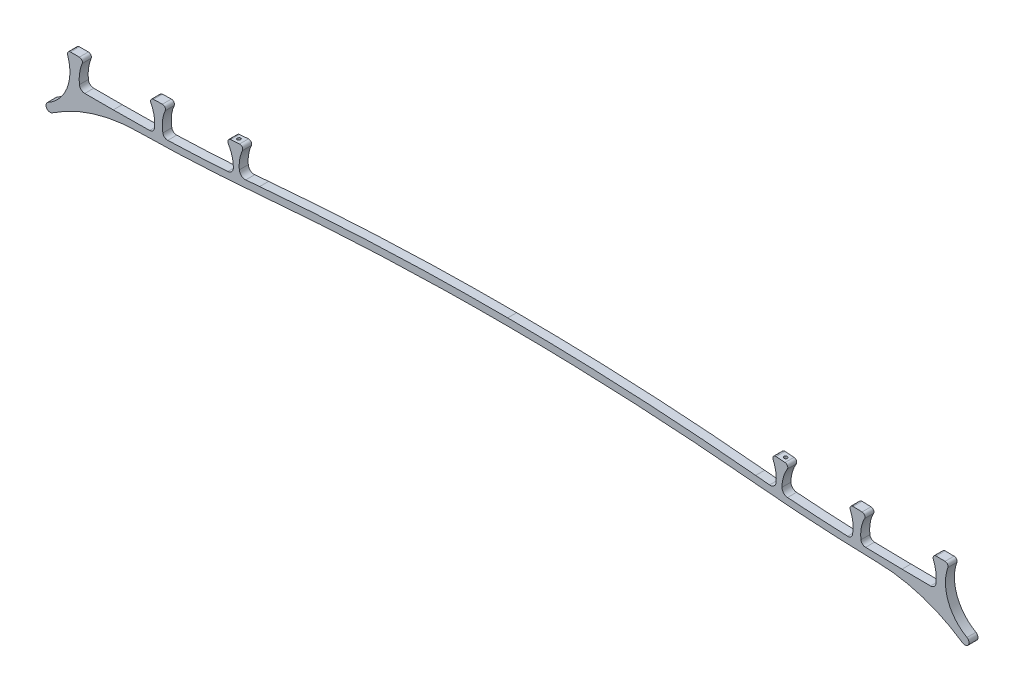
SolidWorks part; units mm, degrees
ref_plane "Front Plane" through (0, 0, 0) normal (0, 0, 1) x (1, 0, 0)
ref_plane "Top Plane" through (0, 0, 0) normal (0, 1, 0) x (1, 0, 0)
ref_plane "Right Plane" through (0, 0, 0) normal (1, 0, 0) x (0, 0, -1)
sketch "Sketch1" plane through (0, 0, 4.0971) normal (0, 0, -1) x (-1, 0, 0)
  line L0 (-62.7619, -51.7222) -> (-58.001, -51.5972) construction
  line L1 (-62.7619, -51.7222) -> (-58.001, -51.5972)
  line L2 (-250.1152, -63.0874) -> (-250.684, -56.8905) construction
  line L3 (-250.1152, -63.0874) -> (-250.684, -56.8905)
  line L4 (5.0134, -50.6875) -> (4.8506, -13.0704)
  line L5 (293.8258, -32.3629) -> (292.5411, -55.9947)
  line L6 (459.2981, -30.7507) -> (468.8231, -30.7507)
  line L7 (423.3798, -61.2307) -> (453.91, -61.2307)
  line L10 (423.2417, -37.1007) -> (607.4086, -37.1007) construction
  line L11 (270.0646, -24.076) -> (423.3798, -30.7507) construction
  line L12 (269.6518, -30.414) -> (423.1036, -37.0947) construction
  line L13 (270.0646, -24.076) -> (423.3798, -30.7507) construction
  line L14 (269.6518, -30.414) -> (423.2417, -37.1007) construction
  line L15 (270.0646, -24.076) -> (423.3798, -30.7507) construction
  line L16 (268.1133, -54.0366) -> (422.0742, -60.7394) construction
  line L17 (268.1133, -54.0366) -> (282.8559, -55.2703)
  line L39 (464.0606, -30.7507) -> (464.0606, -61.2307)
  line L43 (423.3798, -61.2307) -> (607.4086, -61.2307) construction
  line L44 (375.9837, -30.118) -> (375.1663, -60.587)
  line L45 (423.3798, -30.7507) -> (607.4086, -30.7507) construction
  arc A10 (295.9963, -50.7756) -> (301.9161, -57.1188) centre (302.3463, -50.7834) ccw
  arc A11 (301.4662, -31.1688) -> (298.9719, -26.3615) centre (298.7477, -29.5285) ccw
  arc A12 (289.4896, -25.6646) -> (286.3657, -30.1613) centre (289.2483, -28.8304) ccw
  arc A13 (282.8559, -55.2703) -> (289.7096, -49.5155) centre (283.3855, -48.9424) ccw
  arc A17 (301.4662, -31.1688) -> (295.9963, -50.7756) centre (334.0387, -50.8222) ccw
  arc A18 (289.7096, -49.5155) -> (286.3657, -30.1613) centre (251.8722, -46.0867) ccw
  circle A19 centre (490.3927, -92.6507) radius 4.3495
  arc A24 (383.4811, -34.8689) -> (379.749, -56.3925) centre (415.8403, -51.5652) ccw
  circle A29 centre (384.8064, -55.7161) radius 5.1024
  arc A30 (471.8244, -34.9614) -> (468.8231, -30.7507) centre (468.8231, -33.9257) ccw
  arc A31 (459.2981, -30.7507) -> (456.3562, -35.1198) centre (459.2981, -33.9257) ccw
  circle A32 centre (453.6208, -55.4881) radius 5.7427
  arc A33 (383.4811, -34.8689) -> (380.7361, -30.239) centre (380.6595, -33.4131) ccw
  arc A36 (459.3328, -56.0812) -> (456.3562, -35.1198) centre (415.8403, -51.5652) ccw
  arc A39 (368.2424, -34.4601) -> (371.2316, -29.9841) centre (371.1379, -33.1577) cw
  arc A40 (368.2424, -34.4601) -> (370.815, -56.1528) centre (335.0345, -49.3973) cw
  circle A41 centre (365.8012, -55.2062) radius 5.1024
  arc A42 (487.9615, -96.2573) -> (398.3517, -68.1968) centre (396.0818, -232.558) ccw
  arc A43 (471.8244, -34.9614) -> (492.4999, -88.8458) centre (514.2362, -49.5967) ccw
  spline S20 degree 1 poles (365398.7093, 9550.0677) (-365528.5829, -9653.6266) knots -76761.79708 -76761.79708 76766.710756 76766.710756 only from (-53.2401, -51.4722) to (-58.001, -51.5972) construction
  spline S21 degree 1 poles (-53.2401, -51.4722) (-58.001, -51.5972) knots 0 0 1 1
  spline S22 degree 3 poles (-365285.4315, -17668.8025) (-121868.5497, -5930.4401) (121639.8359, 5823.1929) (365056.7131, 17561.5545) knots -76767.936822 -76767.936822 -76767.936822 -76767.936822 76772.733508 76772.733508 76772.733508 76772.733508 only from (-125.7663, -54.1741) to (-121.0093, -53.9446) construction
  spline S23 degree 1 poles (365037.0811, 17563.3216) (-365292.96, -17671.8796) knots -76761.79708 -76761.79708 76766.710756 76766.710756 only from (-116.2524, -53.7151) to (-121.0093, -53.9446) construction
  spline S24 degree 3 poles (-125.7663, -54.1741) (-124.1807, -54.0976) (-122.595, -54.0211) (-121.0093, -53.9446) knots 0 0 0 0 1 1 1 1
  spline S25 degree 1 poles (-116.2524, -53.7151) (-121.0093, -53.9446) knots 0 0 1 1
  spline S26 degree 3 poles (-364867.1723, -25708.7927) (-121740.435, -8582.2589) (121386.2538, 8467.8747) (364512.9914, 25594.4127) knots -76761.79708 -76761.79708 -76761.79708 -76761.79708 76766.710756 76766.710756 76766.710756 76766.710756 only from (-188.7625, -58.0119) to (-184.0117, -57.678) construction
  spline S27 degree 1 poles (364499.1369, 25574.3377) (-364881.0025, -25690.6666) knots -76761.79708 -76761.79708 76766.710756 76766.710756 only from (-179.2609, -57.3441) to (-184.0117, -57.678) construction
  spline S28 degree 3 poles (-188.7625, -58.0119) (-187.1789, -57.9006) (-185.5953, -57.7893) (-184.0117, -57.678) knots 0 0 0 0 1 1 1 1
  spline S29 degree 1 poles (-179.2609, -57.3441) (-184.0117, -57.678) knots 0 0 1 1
  spline S30 degree 3 poles (-364305.982, -33474.3933) (-121635.3274, -11204.5949) (121157.2277, 11080.4514) (363827.8766, 33350.2492) knots -76769.871158 -76769.871158 -76769.871158 -76769.871158 76774.537277 76774.537277 76774.537277 76774.537277 only from (-250.1152, -63.0874) to (-245.3727, -62.6521) construction
  spline S31 degree 1 poles (363807.4185, 33349.3866) (-364311.9821, -33475.959) knots -76761.79708 -76761.79708 76766.710756 76766.710756 only from (-240.6301, -62.2168) to (-245.3727, -62.6521) construction
  spline S32 degree 3 poles (-250.1152, -63.0874) (-248.5344, -62.9423) (-246.9535, -62.7972) (-245.3727, -62.6521) knots 0 0 0 0 1 1 1 1
  spline S33 degree 1 poles (-240.6301, -62.2168) (-245.3727, -62.6521) knots 0 0 1 1
  spline S34 degree 3 poles (-350128.8904, 74318.7235) (10485.7487, 34558.1951) (5966.5817, 298.6907) (-6638.7837, -362.7031) (-14717.7957, 33230.7694) (339737.2718, 110464.3572) knots -40.372141 -40.372141 -40.372141 -40.372141 0.498012 0.498012 41.365106 41.365106 41.365106 41.365106 only from (-260.2582, -26.3703) to (-413.5099, -34.3711) construction
  spline S35 degree 3 poles (-260.2582, -26.3703) (-285.573, -28.8027) (-310.9405, -30.6861) (-362.0399, -33.3672) (-387.7725, -34.1516) (-413.5099, -34.3711) knots 0.333333 0.333333 0.333333 0.333333 0.498012 0.498012 0.664679 0.664679 0.664679 0.664679
  spline S36 degree 3 poles (349486.6475, 77297.8492) (-10774.353, 34462.8749) (-5959.0368, 247.093) (6651.6056, -305.2332) (14440.0911, 33360.4954) (-340666.9575, 107568.7182) knots -40.368098 -40.368098 -40.368098 -40.368098 0.5 0.5 41.36933 41.36933 41.36933 41.36933 only from (270.0646, -24.076) to (423.3798, -30.7507) construction
  spline S37 degree 3 poles (270.0646, -24.076) (295.3995, -26.2893) (320.7823, -27.9531) (371.903, -30.1921) (397.6415, -30.7539) (423.3798, -30.7507) knots 0.335321 0.335321 0.335321 0.335321 0.5 0.5 0.666667 0.666667 0.666667 0.666667
  spline S38 degree 3 poles (34138.9621, 362358.8922) (5323.4883, -4754.5531) (2933.9516, -226.1752) (225.9514, -20.5338) (214.915, -19.7614) (181.7932, -17.6233) (159.6926, -16.4536) (115.476, -14.6188) (93.3552, -13.9534) (60.1689, -13.3398) (49.1062, -13.195) (-2718.3229, 6.5786) (-5521.3328, -4442.3649) (-4432.215, 363984.6204) knots -30.434262 -30.434262 -30.434262 -30.434262 0.125 0.125 0.25 0.25 0.5 0.5 0.75 0.75 0.875 0.875 32.017836 32.017836 32.017836 32.017836 only from (270.0646, -24.076) to (4.8506, -13.0704) construction
  spline S39 degree 3 poles (-37196.4162, 362061.8644) (-5273.4492, -4800.617) (-2922.3434, -251.5149) (-216.1773, -22.4465) (-205.1481, -21.5787) (-172.0462, -19.1541) (-149.9564, -17.7933) (-105.7573, -15.5759) (-83.6432, -14.7191) (-50.4634, -13.8184) (-39.4023, -13.5779) (2727.687, 30.1389) (5568.601, -4394.1839) (1326.2584, 363995.0642) knots -30.434851 -30.434851 -30.434851 -30.434851 0.125 0.125 0.25 0.25 0.5 0.5 0.75 0.75 0.875 0.875 32.017058 32.017058 32.017058 32.017058 only from (-260.2582, -26.3703) to (4.8506, -13.0704) construction
  spline S40 degree 3 poles (270.0646, -24.076) (259.0414, -23.1193) (248.0148, -22.2092) (225.9514, -20.5338) (214.915, -19.7614) (181.7932, -17.6233) (159.6926, -16.4536) (115.476, -14.6188) (93.3552, -13.9534) (60.1689, -13.3398) (49.1062, -13.195) (26.9794, -13.0369) (15.9153, -13.0299) (4.8506, -13.0704) knots 0 0 0 0 0.125 0.125 0.25 0.25 0.5 0.5 0.75 0.75 0.875 0.875 1 1 1 1
  spline S41 degree 3 poles (-260.2582, -26.3703) (-249.2437, -25.3183) (-238.2254, -24.3128) (-216.1773, -22.4465) (-205.1481, -21.5787) (-172.0462, -19.1541) (-149.9564, -17.7933) (-105.7573, -15.5759) (-83.6432, -14.7191) (-50.4634, -13.8184) (-39.4023, -13.5779) (-17.2777, -13.2284) (-6.214, -13.1256) (4.8506, -13.0704) knots 0 0 0 0 0.125 0.125 0.25 0.25 0.5 0.5 0.75 0.75 0.875 0.875 1 1 1 1
  spline S42 degree 1 poles (266.8016, -61.5516) (423.3844, -68.3681) knots 0 0 1 1 construction
  spline S43 degree 1 poles (266.8016, -61.5516) (5.0134, -50.6875) knots 0 0 1 1 construction
  spline S44 degree 1 poles (-256.671, -63.8163) (5.0134, -50.6875) knots 0 0 1 1 construction
  spline S45 degree 1 poles (-256.671, -63.8163) (-413.1891, -71.9871) knots 0 0 1 1 construction
  spline S46 degree 3 poles (423.3844, -68.3681) (417.128, -68.3689) (406.6951, -68.3157) (354.4413, -67.5941) (308.4593, -65.1906) (266.8016, -61.5516) knots 0.335344 0.335344 0.335344 0.335344 0.375021 0.401473 0.666667 0.666667 0.666667 0.666667
  spline S47 degree 3 poles (266.8016, -61.5516) (261.3509, -61.0786) (250.4335, -60.154) (228.7012, -58.4345) (190.549, -55.7631) (136.0425, -52.8693) (81.4825, -51.2368) (43.241, -50.7379) (21.4384, -50.6506) (10.4839, -50.6675) (5.0134, -50.6875) knots 0.00004 0.00004 0.00004 0.00004 0.062532 0.125024 0.250007 0.499973 0.749939 0.874922 0.937414 0.999905 0.999905 0.999905 0.999905
  spline S48 degree 3 poles (5.0134, -50.6875) (-0.4572, -50.7148) (-11.4114, -50.7928) (-33.2124, -51.0686) (-71.4483, -51.8985) (-125.9921, -54.0029) (-180.4716, -57.3683) (-218.5991, -60.3696) (-240.3157, -62.2771) (-251.2247, -63.2961) (-256.671, -63.8163) knots 0.00004 0.00004 0.00004 0.00004 0.062532 0.125023 0.250007 0.499973 0.749939 0.874922 0.937414 0.999905 0.999905 0.999905 0.999905
  spline S49 degree 3 poles (-256.671, -63.8163) (-308.6753, -68.8128) (-360.9473, -71.5416) (-413.1891, -71.9871) knots 0.333356 0.333356 0.333356 0.333356 0.664679 0.664679 0.664679 0.664679
  spline S50 degree 1 poles (267.412, -54.4403) (423.3798, -61.2307) knots 0 0 1 1 construction
  spline S51 degree 1 poles (268.1133, -54.0366) (4.9805, -43.0872) knots 0 0 1 1 construction
  spline S52 degree 1 poles (-257.3958, -56.2506) (4.9805, -43.0872) knots 0 0 1 1 construction
  spline S53 degree 1 poles (-257.3958, -56.2506) (-413.254, -64.3871) knots 0 0 1 1 construction
  spline S54 degree 3 poles (267.412, -54.4403) (276.0285, -55.1931) (290.4062, -56.3442) (313.5674, -57.917) (336.8899, -59.2149) (356.0529, -59.9983) (367.2252, -60.3576) (370.4015, -60.4534) (373.5779, -60.5449) (376.7545, -60.6301) (379.9313, -60.709) (383.1082, -60.7837) (397.5889, -61.095) (411.2827, -61.2322) (423.3798, -61.2307) knots 0.335321 0.335321 0.335321 0.335321 0.390393 0.427108 0.483088 0.539068 0.549181 0.554238 0.559295 0.569408 0.574465 0.579521 0.589635 0.666659 0.666659 0.666659 0.666659 only from (301.9161, -57.1188) to (423.3798, -61.2307)
  spline S55 degree 3 poles (268.1133, -54.0366) (262.6347, -53.5611) (251.6633, -52.6287) (229.8118, -50.8954) (191.4718, -48.2039) (136.6796, -45.2869) (81.8357, -43.6415) (43.4028, -43.1385) (21.4808, -43.0503) (10.477, -43.0671) (4.9805, -43.0872) knots -0.002434 -0.002434 -0.002434 -0.002434 0.060213 0.122861 0.248155 0.498745 0.749335 0.87463 0.937277 0.999924 0.999924 0.999924 0.999924
  spline S56 degree 3 poles (4.9805, -43.0872) (-0.5025, -43.1146) (-11.479, -43.1927) (-33.3456, -43.4694) (-71.6781, -44.3013) (-126.3714, -46.4114) (-181.0006, -49.7861) (-219.224, -52.795) (-241.0064, -54.7082) (-251.9372, -55.7293) (-257.3958, -56.2506) knots 0.000032 0.000032 0.000032 0.000032 0.062525 0.125019 0.250005 0.499978 0.749951 0.874938 0.937431 0.999924 0.999924 0.999924 0.999924
  spline S57 degree 3 poles (-257.3958, -56.2506) (-309.1808, -61.2261) (-361.2324, -63.9435) (-413.254, -64.3871) knots 0.333351 0.333351 0.333351 0.333351 0.664679 0.664679 0.664679 0.664679
  spline S59 degree 3 poles (-413.1844, -71.9874) (-456.1014, -80.1224) (-434.4954, -79.3287) (-479.9907, -101.3371) (-478.4868, -100.9323) knots 0 0 0 0 0.938514 1 1 1 1
  spline S61 degree 1 poles (269.6518, -30.414) (4.8739, -19.4204) knots 0 0 1 1 construction
  spline S63 degree 3 poles (4.8739, -19.4204) (26.9656, -19.3394) (71.1539, -19.6344) (137.3995, -21.6337) (203.5831, -25.1323) (247.6429, -28.5039) (269.6518, -30.414) knots -0.000515 -0.000515 -0.000515 -0.000515 0.249614 0.499743 0.749871 1 1 1 1
  spline S66 degree 1 poles (269.6518, -30.414) (4.8739, -19.4204) knots 0 0 1 1 construction
  spline S68 degree 3 poles (4.8739, -19.4204) (26.9656, -19.3394) (71.1539, -19.6344) (137.3995, -21.6337) (203.5831, -25.1323) (247.6429, -28.5039) (269.6518, -30.414) knots -0.000515 -0.000515 -0.000515 -0.000515 0.249614 0.499743 0.749871 1 1 1 1
  point P81 (310.3019, -33.4897)
  dimension "D3" = 30.48
  dimension "D5" = 6.35
  dimension "D8" = 4.7625
  dimension "D9" = 3.175
  dimension "D10" = 9.525
  dimension "D11" = 12.7
  dimension "D12" = 19.05
  dimension "D16" = 12.7
  dimension "D17" = 3.175
  dimension "D18" = 4.7625
  dimension "D19" = 4.7625
  dimension "D13" = 9.525
  dimension "D14" = 4.7625
  dimension "D15" = 25.4
  dimension "D1" = 37.6174
  dimension "D7" = 6.35
  dimension "D22" = 6.35
extrude "Boss-Extrude5" add sketch "Sketch1" along normal blind 4.7625 and the other way blind 4.7625 contours L7 S54 A10 A17 A11 S37 A12 A18 A13 L17 S55 | A19 | A19 | S54 L44 S37 | L44 S54 A29 A24 A33 S37 region at (-287.273, -56.7987, 4.0971) region at (-490.3927, -92.6507, 4.0971) region at (-372.7453, -43.9651, 4.0971) region at (-378.475, -44.1188, 4.0971)
ref_plane "Plane1" through (0.3209, -4.3662, 0) normal (-0.0733, 0.9973, 0) x (0.9973, 0.0733, 0)
sketch "Sketch6" plane through (0.3209, -4.3662, 0) normal (-0.0733, 0.9973, 0) x (0.9973, 0.0733, 0)
  line L4 (-290.592, -8.8596) -> (-290.592, 0.6654)
  line L10 (-300.0999, 0.6654) -> (-300.0999, -8.8596)
  line L24 (-290.592, -8.8596) -> (-290.592, 0.6654)
  line L27 (-290.592, 0.6654) -> (-300.0999, 0.6654)
  line L29 (-290.592, 0.6654) -> (-300.0999, 0.6654)
  line L30 (-300.0999, -8.8596) -> (-290.592, -8.8596)
  line L31 (-300.0999, -8.8596) -> (-290.592, -8.8596)
  line L34 (-300.0999, 0.6654) -> (-300.0999, -8.8596)
  circle A0 centre (-295.9801, -4.0971) radius 1.778
  dimension "D1" = 0
extrude "Cut-Extrude3" cut sketch "Sketch6" against normal through all contours A0
ref_axis "Axis1" through (-292.1133, -63.4785, 4.0971) along (-0.0733, 0.9973, 0)
ref_plane "Plane2" through (3.0659, -41.7188, 0) normal (-0.0733, 0.9973, 0) x (-0.9947, -0.0731, 0.0729)
sketch "Sketch7" plane through (3.0659, -41.7188, 0) normal (-0.0733, 0.9973, 0) x (-0.9947, -0.0731, 0.0729)
  circle A0 centre (295.4907, -17.5004) radius 1.778 construction
  circle A1 centre (295.4907, -17.5004) radius 1.778
  circle A2 centre (295.4907, -17.5004) radius 3.048
extrude "Cut-Extrude4" cut sketch "Sketch7" along normal blind 3.556 and the other way through all
mirror "Mirror4" about plane through (-4.794, 0.0207, 8.8596) normal (-1, 0.0043, 0) of "Cut-Extrude4", "Cut-Extrude3", "Boss-Extrude5"
